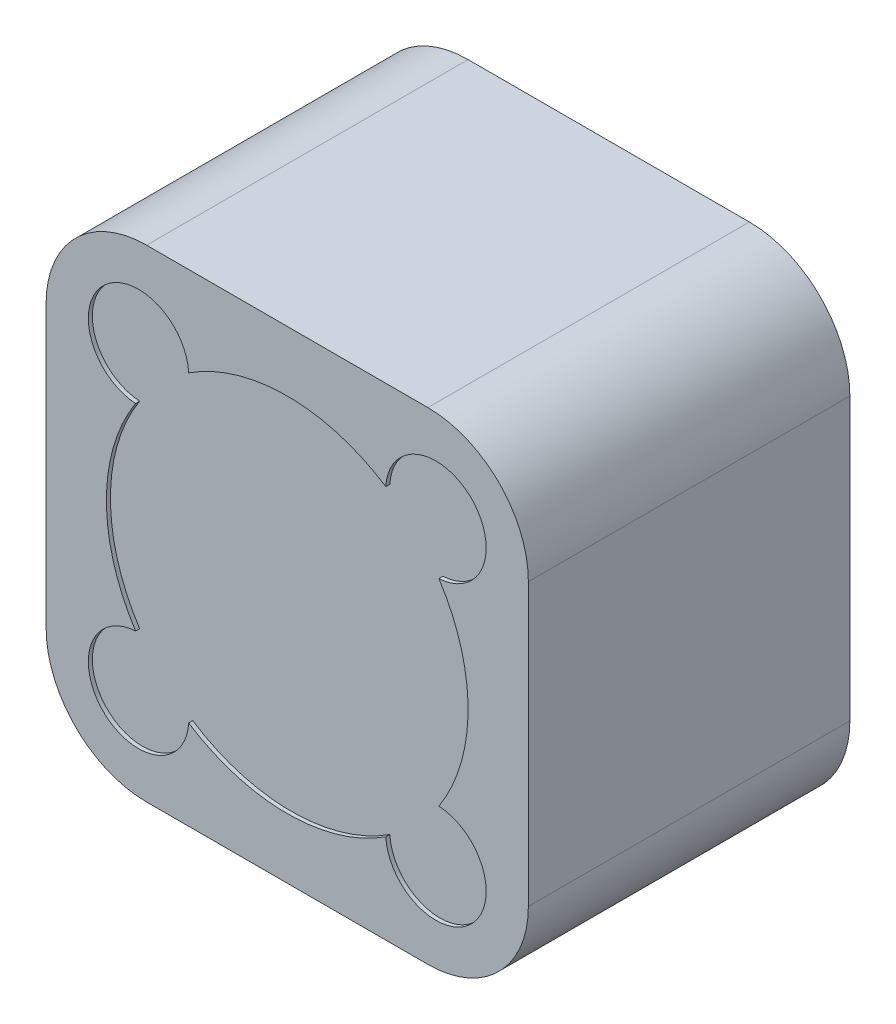
SolidWorks part; units mm, degrees
ref_plane "Спереди" through (0, 0, 0) normal (0, 0, 1) x (1, 0, 0)
ref_plane "Сверху" through (0, 0, 0) normal (0, 1, 0) x (1, 0, 0)
ref_plane "Справа" through (0, 0, 0) normal (1, 0, 0) x (0, 0, -1)
sketch "Эскиз1" plane through (0, 0, 0) normal (0, 0, 1) x (1, 0, 0)
  line L9 (-6, -6) -> (6, -6)
  line L10 (-6, -6) -> (-6, 6)
  line L11 (-6, 6) -> (6, 6)
  line L12 (6, -6) -> (6, 6)
  line L13 (-6, -6) -> (6, 6) construction
  line L14 (-6, 6) -> (6, -6) construction
  point P0 (0, 0)
  dimension "D1" = 12
extrude "Бобышка-Вытянуть1" add sketch "Эскиз1" along normal blind 8
fillet "Скругление1" radius 2.5 4 edges at (-6, 6, 4) (6, 6, 4) (-6, -6, 4) (6, -6, 4)
sketch "Эскиз2" plane through (0, 0, 8) normal (0, 0, 1) x (1, 0, 0)
  circle A0 centre (0, 0) radius 4.5
  point P3 (0, 0)
  dimension "D1" = 9
extrude "Вырез-Вытянуть1" cut sketch "Эскиз2" against normal blind 0.1
sketch "Эскиз3" plane through (0, 0, 8) normal (0, 0, 1) x (1, 0, 0)
  circle A0 centre (-3.7, -3.7) radius 1.25
  dimension "D2" = 2.5
  dimension "D1" = 3.7
  dimension "D3" = 3.7
extrude "Вырез-Вытянуть2" cut sketch "Эскиз3" against normal blind 0.1
ref_axis "Ось1" through (0, 0, -0.4) along (0, 0, 1)
pattern_circular "Круговой массив1" count 4 over 360 about axis through (0, 0, -0.4) along (0, 0, 1) of "Вырез-Вытянуть2"
